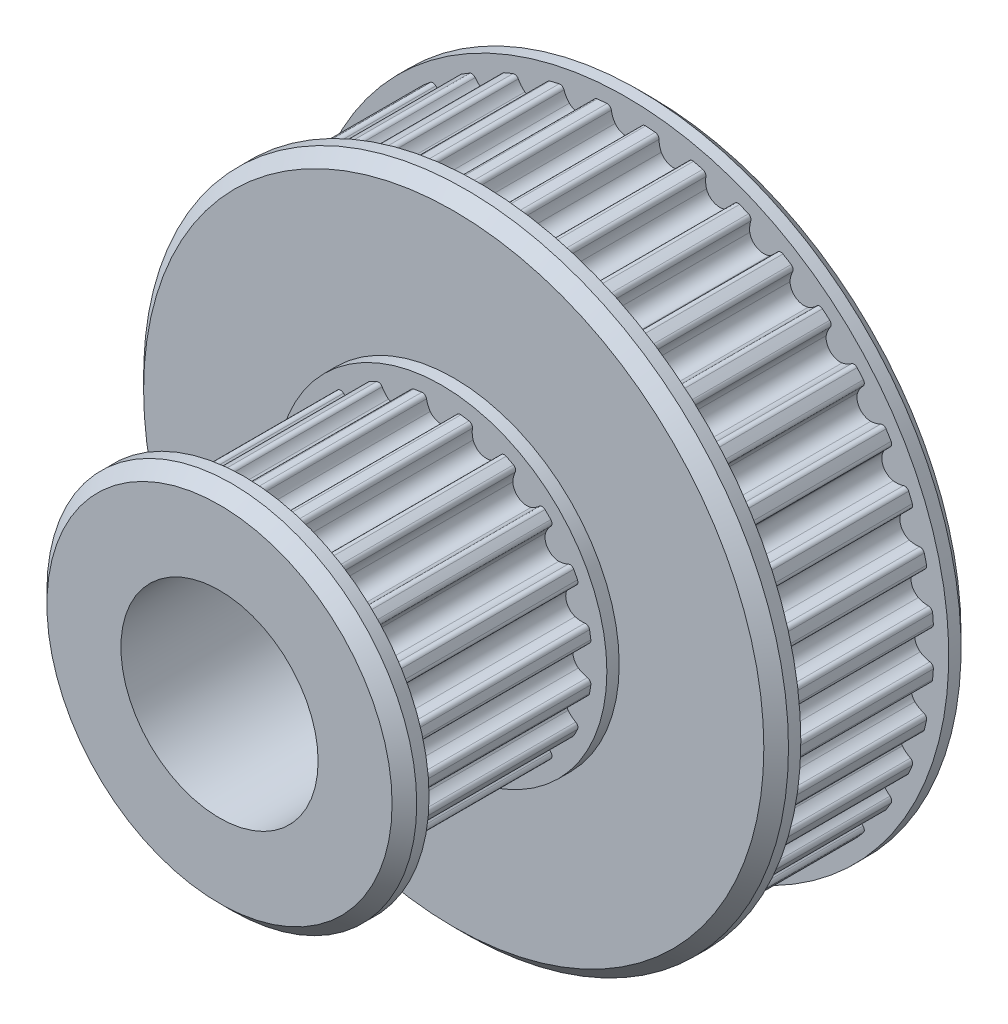
SolidWorks part; units mm, degrees
ref_plane "Front Plane" through (0, 0, 0) normal (0, 0, 1) x (1, 0, 0)
ref_plane "Top Plane" through (0, 0, 0) normal (0, 1, 0) x (1, 0, 0)
ref_plane "Right Plane" through (0, 0, 0) normal (1, 0, 0) x (0, 0, -1)
sketch "Sketch1" plane through (0, 0, 0) normal (0, 0, 1) x (1, 0, 0)
  circle A0 centre (0, 0) radius 12.4784
  dimension "D1" = 24.9568
extrude "Boss-Extrude1" add sketch "Sketch1" along normal blind 6
sketch "Sketch2" plane through (0, 0, 6) normal (0, 0, 1) x (1, 0, 0)
  line L0 (0, 0) -> (0, 11.7184) construction
  line L1 (0, 12.4784) -> (0.4, 12.4784) construction
  line L2 (0, 12.4784) -> (-0.4, 12.4784) construction
  line L3 (0, 12.2734) -> (0, 12.4784) construction
  arc A0 (0.6199, 12.463) -> (-0.6199, 12.463) centre (0, 0) ccw
  circle A1 centre (0, 0) radius 12.2734 construction
  circle A2 centre (0, 0) radius 11.7184 construction
  arc A4 (0.4536, 11.92) -> (0.6199, 12.463) centre (-0.4, 12.4784) ccw
  arc A5 (-0.4536, 11.92) -> (0.4536, 11.92) centre (0, 12.2734) ccw
  arc A6 (-0.6199, 12.463) -> (-0.4536, 11.92) centre (0.4, 12.4784) ccw
  dimension "D1" = 24.9568
  dimension "D2" = 24.5468
  dimension "D3" = 23.4368
  dimension "D6" = 2.04
  dimension "D8" = 1.15
  dimension "D4" = 0.4
  dimension "D5" = 0.4
extrude "Cut-Extrude1" cut sketch "Sketch2" against normal blind 8
fillet "Fillet1" radius 0.17 2 edges at (0.6199, 12.463, 3) (-0.6199, 12.463, 3)
ref_axis "Axis1" through (0, 0, 6) along (0, 0, -1)
pattern_circular "CirPattern1" count 40 over 360 about axis through (0, 0, 6) along (0, 0, -1) of "Cut-Extrude1", "Fillet1"
sketch "Sketch3" plane through (0, 0, 6) normal (0, 0, 1) x (1, 0, 0)
  circle A0 centre (0, 0) radius 13.0784
  dimension "D1" = 26.1568
extrude "Boss-Extrude2" add sketch "Sketch3" along normal blind 1
sketch "Sketch4" plane through (0, 0, 0) normal (0, 0, -1) x (-1, 0, 0)
  circle A0 centre (0, 0) radius 13.0784
  dimension "D1" = 26.1568
extrude "Boss-Extrude3" add sketch "Sketch4" along normal blind 1
chamfer "Chamfer1" distance 0.5 angle 45 2 edges at (13.0784, 0, 7) (-13.0784, 0, -1)
sketch "Sketch5" plane through (0, 0, 7) normal (0, 0, 1) x (1, 0, 0)
  circle A0 centre (0, 0) radius 6.7122
  dimension "D1" = 13.4244
extrude "Boss-Extrude4" add sketch "Sketch5" along normal blind 0.5
sketch "Sketch6" plane through (0, 0, 7.5) normal (0, 0, 1) x (1, 0, 0)
  circle A0 centre (0, 0) radius 6.1122
  dimension "D1" = 12.2244
extrude "Boss-Extrude5" add sketch "Sketch6" along normal blind 8
sketch "Sketch7" plane through (0, 0, 15.5) normal (0, 0, 1) x (1, 0, 0)
  line L0 (0, 0) -> (0, 5.3522) construction
  line L1 (0, 6.1122) -> (-0.4, 6.1122) construction
  line L2 (0, 6.1122) -> (0.4, 6.1122) construction
  line L3 (0, 5.9072) -> (0, 6.1122) construction
  arc A0 (0.6195, 6.0807) -> (-0.6195, 6.0807) centre (0, 0) ccw
  circle A1 centre (0, 0) radius 5.9072 construction
  circle A2 centre (0, 0) radius 5.3522 construction
  arc A3 (0.4536, 5.5538) -> (0.6195, 6.0807) centre (-0.4, 6.1122) ccw
  arc A5 (-0.4536, 5.5538) -> (0.4536, 5.5538) centre (0, 5.9072) ccw
  arc A6 (-0.6195, 6.0807) -> (-0.4536, 5.5538) centre (0.4, 6.1122) ccw
  dimension "D6" = 2.04
  dimension "D8" = 1.15
  dimension "D4" = 0.4
  dimension "D5" = 0.4
  dimension "D1" = 12.2244
  dimension "D2" = 11.8144
  dimension "D3" = 10.7044
extrude "Cut-Extrude2" cut sketch "Sketch7" against normal blind 8
fillet "Fillet4" radius 0.17 2 edges at (0.6195, 6.0807, 11.5) (-0.6195, 6.0807, 11.5)
ref_axis "Axis2" through (0, 0, 15.5) along (0, 0, -1)
pattern_circular "CirPattern2" count 20 over 360 about axis through (0, 0, 15.5) along (0, 0, -1) of "Cut-Extrude2", "Fillet4"
sketch "Sketch8" plane through (0, 0, 15.5) normal (0, 0, 1) x (1, 0, 0)
  circle A0 centre (0, 0) radius 6.7122
  dimension "D1" = 13.4244
extrude "Boss-Extrude6" add sketch "Sketch8" along normal blind 1
sketch "Sketch9" plane through (0, 0, 16.5) normal (0, 0, 1) x (1, 0, 0)
  circle A0 centre (0, 0) radius 4
  dimension "D1" = 8
extrude "Cut-Extrude3" cut sketch "Sketch9" against normal through all
ref_plane "Plane1" through (0, 0, 4) normal (0, 0, 1) x (1, 0, 0)
sketch "Sketch10" plane through (0, 0, 4) normal (0, 0, 1) x (1, 0, 0)
  circle A0 centre (0, 0) radius 12.4784 construction
  dimension "D1" = 24.9568
ref_plane "Plane2" through (0, 0, 11.5) normal (0, 0, 1) x (1, 0, 0)
sketch "Sketch12" plane through (0, 0, 11.5) normal (0, 0, 1) x (1, 0, 0)
  circle A0 centre (0, 0) radius 6.1122 construction
  dimension "D1" = 12.2244
sketch "Sketch13" plane through (0, 0, 16.5) normal (0, 0, 1) x (1, 0, 0)
  circle A0 centre (0, 0) radius 4
  circle A1 centre (0, 0) radius 7.5
  dimension "D1" = 15
extrude "Boss-Extrude7" add sketch "Sketch13" against normal blind 1
chamfer "Chamfer2" distance 0.5 angle 45 1 edges at (7.5, 0, 16.5)
equation "\"GD\"= 0.76mm'Groove Depths"
equation "\"SBD\"= 2mm'Pitch"
equation "\"NT\"= 40'Number of Teeth"
equation "\"PD\"= ( \"SBD\" * \"NT\" ) / 3.14159'Pitch Diameter"
equation "\"U\"= 0.254mm"
equation "\"OD\"= \"PD\" - ( 2 * \"U\" )'Outside Diameter"
equation "\"RD\"= \"OD\" - ( 2 * \"GD\" )'Root Diameter"
equation "\"R3\"= 0.555mm"
equation "\"R2\"= 1mm"
equation "\"R1\"= 0.15mm"
equation "\"DT\"= 0.02mm'Tolerance"
equation "\"b\"= 0.4mm"
equation "\"D1@Sketch1\"= \"OD\""
equation "\"D1@Sketch2\"= \"OD\""
equation "\"D2@Sketch2\"= \"RD\" + \"R3\" * 2"
equation "\"D3@Sketch2\"= \"RD\""
equation "\"D4@Sketch2\"= \"b\""
equation "\"D5@Sketch2\"= \"b\""
equation "\"D6@Sketch2\" = ( \"R2\" + \"DT\" ) * 2"
equation "\"D8@Sketch2\"= ( \"R3\" + \"DT\" ) * 2"
equation "\"D1@Fillet1\"=\"R1\" + \"DT\""
equation "\"D1@CirPattern1\"=\"NT\""
equation "\"D1@Sketch3\"= \"OD\" + 1.2"
equation "\"D1@Sketch4\"= \"OD\" + 1.2"
equation "\"NT2\"= 20"
equation "\"PD2\"= ( \"SBD\" * \"NT2\" ) / 3.14159"
equation "\"OD2\"= \"PD2\" - ( 2 * \"U\" )"
equation "\"RD2\"= \"OD2\" - ( 2 * \"GD\" )"
equation "\"D1@Sketch6\"= \"OD2\""
equation "\"D1@Sketch7\"= \"OD2\""
equation "\"D2@Sketch7\"= \"RD2\" + \"R3\" * 2"
equation "\"D3@Sketch7\"= \"RD2\""
equation "\"D4@Sketch7\"= \"b\""
equation "\"D5@Sketch7\"= \"b\""
equation "\"D6@Sketch7\"= ( \"R2\" + \"DT\" ) * 2"
equation "\"D8@Sketch7\"= ( \"R3\" + \"DT\" ) * 2"
equation "\"D1@Fillet4\"=\"R1\" + \"DT\""
equation "\"D1@CirPattern2\"=\"NT2\""
equation "\"D1@Sketch5\"= \"OD2\" + 1.2"
equation "\"D1@Sketch8\"= \"OD2\" + 1.2"
equation "\"D1@Sketch10\"= \"OD\""
equation "\"D1@Sketch12\"= \"OD2\""
